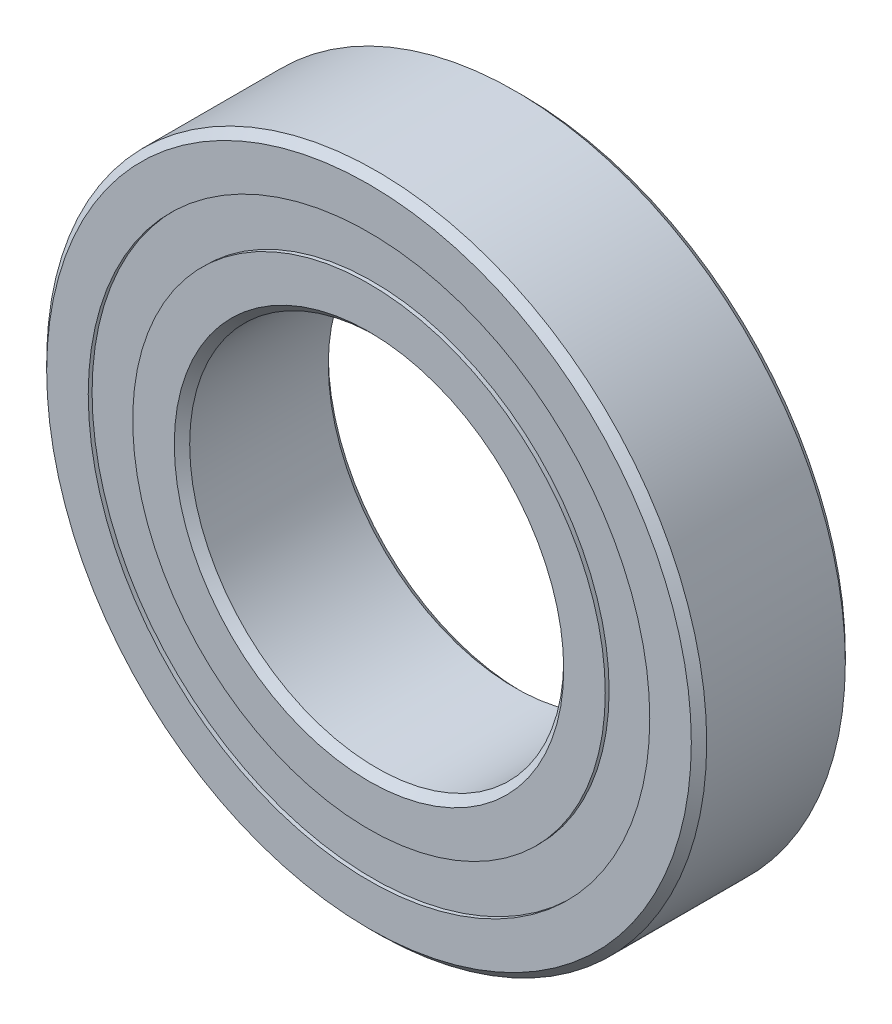
SolidWorks part; units mm, degrees
material "AISI 1020 Steel, Cold Rolled"
ref_plane "Front Plane" through (0, 0, 0) normal (0, 0, 1) x (1, 0, 0)
ref_plane "Top Plane" through (0, 0, 0) normal (0, 1, 0) x (1, 0, 0)
ref_plane "Right Plane" through (0, 0, 0) normal (1, 0, 0) x (0, 0, -1)
sketch "Sketch1" plane through (0, 0, 0) normal (0, 0, 1) x (1, 0, 0)
  circle A0 centre (0, 0) radius 15 construction
  circle A1 centre (0, 0) radius 8.5 construction
  dimension "OD" = 30
  dimension "Shaft Dia" = 17
sketch "Sketch2" plane through (0, 0, 0) normal (1, 0, 0) x (0, 0, -1)
  line L0 (-3.5, 0) -> (3.5, 0) construction
  line L1 (0, 15) -> (0, -15) construction
  line L2 (3.15, 15) -> (-3.15, 15) construction
  line L3 (-3.15, 15) -> (-3.5, 14.65) construction
  line L4 (-3.5, 14.65) -> (-3.5, 12.761) construction
  line L5 (-3.5, 12.761) -> (-1.5556, 12.761) construction
  line L6 (3.5, 12.761) -> (1.5556, 12.761) construction
  line L7 (3.5, 14.65) -> (3.5, 12.761) construction
  line L8 (3.15, 15) -> (3.5, 14.65) construction
  line L9 (0, 15) -> (0, 11.75) construction
  line L10 (0, 11.75) -> (0, 8.5) construction
  line L11 (3.5, 11.75) -> (-3.5, 11.75) construction
  line L12 (-3.5, 8.85) -> (-3.5, 10.739) construction
  line L13 (-3.15, 8.5) -> (-3.5, 8.85) construction
  line L14 (3.15, 8.5) -> (-3.15, 8.5) construction
  line L15 (3.15, 8.5) -> (3.5, 8.85) construction
  line L16 (3.5, 8.85) -> (3.5, 10.739) construction
  line L17 (3.5, 10.739) -> (1.5556, 10.739) construction
  line L18 (-3.5, 10.739) -> (-1.5556, 10.739) construction
  arc A0 (-1.5556, 12.761) -> (1.5556, 12.761) centre (0, 11.75) cw construction
  arc A1 (-1.5556, 10.739) -> (1.5556, 10.739) centre (0, 11.75) ccw construction
  point P14 (0, 8.5)
  point P18 (0, 11.75)
  dimension "D1" = 45
  dimension "D2" = 0.35
  dimension "D3" = 3.1111
  dimension "D4" = 1.011
  dimension "Width" = 7
sketch "Sketch6" plane through (0, 0, 0) normal (1, 0, 0) x (0, 0, -1)
  line L0 (-3.5, 14.65) -> (-3.5, 12.761) construction
  line L1 (-3.15, 15) -> (-3.5, 14.65) construction
  line L2 (3.15, 15) -> (-3.15, 15) construction
  line L3 (3.15, 15) -> (3.5, 14.65) construction
  line L4 (3.5, 14.65) -> (3.5, 12.761) construction
  line L5 (3.5, 12.761) -> (1.5556, 12.761) construction
  line L6 (-3.5, 12.761) -> (-1.5556, 12.761) construction
  line L7 (-3.5, 14.65) -> (-3.5, 12.761)
  line L8 (-3.15, 15) -> (-3.5, 14.65)
  line L9 (3.15, 15) -> (-3.15, 15)
  line L10 (3.15, 15) -> (3.5, 14.65)
  line L11 (3.5, 14.65) -> (3.5, 12.761)
  line L12 (3.5, 12.761) -> (1.5556, 12.761)
  line L13 (-3.5, 12.761) -> (-1.5556, 12.761)
  line L14 (-3.5, 8.85) -> (-3.5, 10.739) construction
  line L15 (-3.15, 8.5) -> (-3.5, 8.85) construction
  line L16 (3.15, 8.5) -> (-3.15, 8.5) construction
  line L17 (3.15, 8.5) -> (3.5, 8.85) construction
  line L18 (3.5, 8.85) -> (3.5, 10.739) construction
  line L19 (3.5, 10.739) -> (1.5556, 10.739) construction
  line L20 (-3.5, 10.739) -> (-1.5556, 10.739) construction
  line L21 (-3.5, 8.85) -> (-3.5, 10.739)
  line L22 (-3.15, 8.5) -> (-3.5, 8.85)
  line L23 (3.15, 8.5) -> (-3.15, 8.5)
  line L24 (3.15, 8.5) -> (3.5, 8.85)
  line L25 (3.5, 8.85) -> (3.5, 10.739)
  line L26 (3.5, 10.739) -> (1.5556, 10.739)
  line L27 (-3.5, 10.739) -> (-1.5556, 10.739)
  arc A0 (1.5556, 12.761) -> (-1.5556, 12.761) centre (0, 11.75) ccw construction
  arc A1 (1.5556, 12.761) -> (-1.5556, 12.761) centre (0, 11.75) ccw
  arc A2 (-1.5556, 10.739) -> (1.5556, 10.739) centre (0, 11.75) ccw construction
  arc A3 (-1.5556, 10.739) -> (1.5556, 10.739) centre (0, 11.75) ccw
revolve "Revolve1" add sketch "Sketch6" angle 360 about L0
sketch "Sketch4" plane through (0, 0, 0) normal (1, 0, 0) x (0, 0, -1)
  line L0 (-1.8552, 11.75) -> (1.8552, 11.75)
  arc A2 (-1.8552, 11.75) -> (1.8552, 11.75) centre (0, 11.75) cw
  arc A3 (1.5556, 12.761) -> (-1.5556, 12.761) centre (0, 11.75) ccw construction
revolve "Revolve2" add sketch "Sketch4" angle 360 about L0
ref_axis "Axis1" through (0, 0, -3.5) along (0, 0, 1)
pattern_circular "CirPattern1" count 12 every 30 about axis through (0, 0, -3.5) along (0, 0, 1) of bodies 104
sketch "Sketch5" plane through (0, 0, 0) normal (1, 0, 0) x (0, 0, -1)
  line L0 (-3.5, 12.761) -> (-1.5556, 12.761) construction
  line L1 (-3.325, 12.761) -> (-1.8552, 12.761)
  line L2 (-3.325, 12.761) -> (-3.325, 10.739)
  line L3 (-3.325, 10.739) -> (-1.8552, 10.739)
  line L4 (-1.8552, 12.761) -> (-1.8552, 10.739)
  line L6 (3.5, 12.761) -> (1.5556, 12.761) construction
  line L7 (3.325, 12.761) -> (1.8552, 12.761)
  line L8 (3.325, 12.761) -> (3.325, 10.739)
  line L9 (3.325, 10.739) -> (1.8552, 10.739)
  line L10 (1.8552, 12.761) -> (1.8552, 10.739)
  line L12 (-3.15, 15) -> (-3.5, 14.65) construction
  line L13 (-3.5, 10.739) -> (-1.5556, 10.739) construction
  line L14 (3.5, 10.739) -> (1.5556, 10.739) construction
  point P18 (-3.325, 14.825)
revolve "Revolve3" add sketch "Sketch5" angle 360 about L0
equation "\"D2@Sketch2\"= \"Width@Sketch2\" * .05"
equation "\"D3@Sketch2\"=\"Width@Sketch2\" / 2.25"
equation "\"D4@Sketch2\"= ( ( ( \"OD@Sketch1\" - \"Width@Sketch2\" ) / 2 ) / 3.25 ) / 3.5"
equation "\"D2@CirPattern1\" = 360/\"Balls@CirPattern1\""
